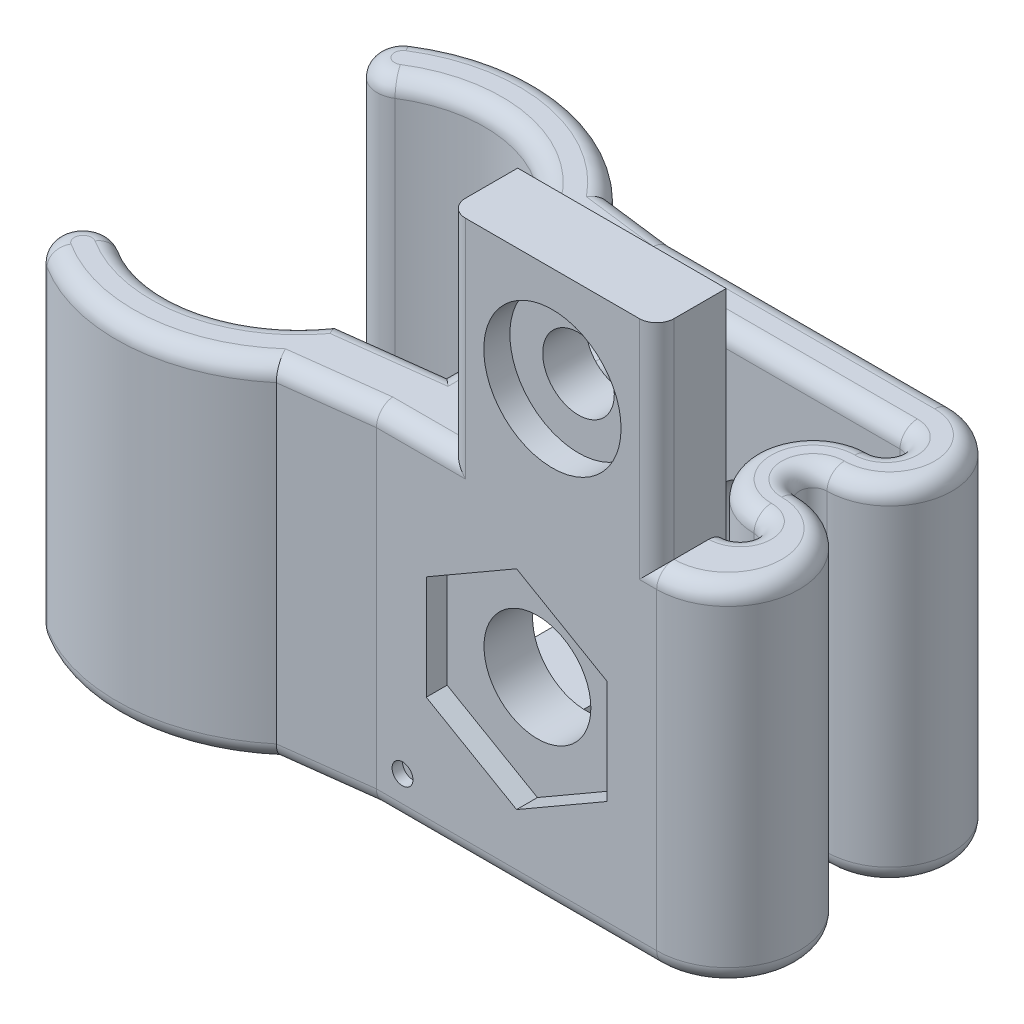
SolidWorks part; units mm, degrees
ref_plane "Front Plane" through (0, 0, 0) normal (0, 0, 1) x (1, 0, 0)
ref_plane "Top Plane" through (0, 0, 0) normal (0, 1, 0) x (1, 0, 0)
ref_plane "Right Plane" through (0, 0, 0) normal (1, 0, 0) x (0, 0, -1)
sketch "Sketch2" plane through (0, 0, 0) normal (0, 1, 0) x (1, 0, 0)
  line L0 (0, 0) -> (28, 0) construction
  line L1 (0, 0) -> (0, 1.6) construction
  line L2 (0, 0) -> (0, -1.6) construction
  line L3 (28, 0) -> (28, 5) construction
  line L4 (28, 0) -> (28, -5) construction
  line L5 (28, 5) -> (6, 5) construction
  line L6 (28, -5) -> (6, -5) construction
  line L7 (11.8739, 5) -> (28, 5)
  line L8 (11.8739, -5) -> (28, -5)
  line L9 (28, 8) -> (11.8739, 8)
  line L10 (28, -9) -> (11.8739, -9)
  line L11 (11.8739, 5) -> (6.2801, 5.7)
  line L12 (11.8739, 8) -> (7.919, 8.4949)
  line L13 (11.8739, -5) -> (6.2801, -5.7)
  line L14 (11.8739, -9) -> (6.7523, -9.6409)
  arc A0 (6.2801, 5.7) -> (-4, 7.9443) centre (0, 1.6) ccw
  arc A1 (6.2801, -5.7) -> (-4, -7.9443) centre (0, -1.6) cw
  arc A2 (28, 5) -> (28, 3.4) centre (28, 4.2) cw
  arc A3 (28, 3.4) -> (28, -3.4) centre (28, 0) ccw
  arc A4 (28, -3.4) -> (28, -5) centre (28, -4.2) cw
  arc A5 (-4, 7.9443) -> (-5.6, 10.482) centre (-4.8, 9.2131) cw
  arc A6 (-4, -7.9443) -> (-5.6, -10.482) centre (-4.8, -9.2131) ccw
  arc A7 (-5.6, 10.482) -> (7.919, 8.4949) centre (0, 1.6) cw
  arc A8 (-5.6, -10.482) -> (6.7523, -9.6409) centre (0, -1.6) ccw
  arc A9 (28, -9) -> (28, -0.8) centre (28, -4.9) ccw
  arc A10 (28, -0.8) -> (28, 0.8) centre (28, 0) cw
  arc A11 (28, 0.8) -> (28, 8) centre (28, 4.4) ccw
  dimension "D6" = 7.5
  dimension "D7" = 7.5
  dimension "D8" = 0.8
  dimension "D9" = 0.8
  dimension "D11" = 1.5
  dimension "D12" = 1.5
  dimension "D14" = 10.5
  dimension "D16" = 10.5
  dimension "D17" = 0.8
  dimension "D18" = 11.8739
  dimension "D1" = 1.6
  dimension "D2" = 1.6
  dimension "D3" = 28
  dimension "D4" = 5
  dimension "D5" = 5
  dimension "D10" = 4
  dimension "D13" = 3
  dimension "D15" = 4
  dimension "D19" = 0.7
extrude "Boss-Extrude1" add sketch "Sketch2" along normal blind 20
sketch "Sketch3" plane through (0, 0, -8) normal (0, 0, -1) x (-1, 0, 0)
  line L0 (-19.9369, 20) -> (-19.9369, 0) construction
  line L1 (-28, 20) -> (-11.8739, 20) construction
  line L2 (-28, 0) -> (-11.8739, 0) construction
  circle A0 centre (-19.9369, 10) radius 3.075
  dimension "D1" = 6.15
extrude "Cut-Extrude1" cut sketch "Sketch3" against normal through all
sketch "Sketch4" plane through (0, 0, 9) normal (0, 0, 1) x (1, 0, 0)
  line L0 (19.9369, 6.925) -> (19.9369, 13.075) construction
  line L2 (19.9369, 4) -> (25.1331, 7)
  line L3 (25.1331, 7) -> (25.1331, 13)
  line L4 (25.1331, 13) -> (19.9369, 16)
  line L5 (19.9369, 16) -> (14.7408, 13)
  line L6 (14.7408, 13) -> (14.7408, 7)
  line L7 (14.7408, 7) -> (19.9369, 4)
  circle A0 centre (19.9369, 10) radius 3.075 construction
  circle A1 centre (19.9369, 10) radius 6 construction
  dimension "D1" = 12
extrude "Cut-Extrude2" cut sketch "Sketch4" against normal blind 1.2
sketch "Sketch5" plane through (0, 20, 0) normal (0, 1, 0) x (1, 0, 0)
  line L0 (28, -5) -> (11.8739, -5) construction
  line L1 (28, -9) -> (16, -9)
  line L2 (28, -9) -> (28, -5)
  line L3 (28, -5) -> (16, -5)
  line L4 (16, -9) -> (16, -5)
  dimension "D1" = 12
extrude "Boss-Extrude2" add sketch "Sketch5" along normal blind 12
sketch "Sketch6" plane through (0, 0, 9) normal (0, 0, 1) x (1, 0, 0)
  line L0 (16, 26) -> (28, 26) construction
  line L1 (16, 32) -> (16, 20) construction
  line L2 (28, 32) -> (28, 20) construction
  circle A0 centre (22, 26) radius 2.06
  dimension "D1" = 4.12
extrude "Cut-Extrude3" cut sketch "Sketch6" against normal through all
sketch "Sketch7" plane through (0, 0, 0) normal (0, -1, 0) x (1, 0, 0)
  line L0 (11.8739, 5) -> (11.8739, -1.8)
  line L1 (28, 5) -> (11.8739, 5) construction
  line L2 (16.8739, 5) -> (16.8739, -2.3)
  line L3 (11.8739, 5) -> (16.8739, 5)
  line L4 (11.8739, -1.8) -> (16.8739, -2.3)
  dimension "D1" = 11.8739
  dimension "D2" = 6.8
  dimension "D3" = 7.3
  dimension "D4" = 5
extrude "Boss-Extrude3" add sketch "Sketch7" against normal blind 4
extrude "Boss-Extrude4" add sketch "Sketch7<2>" against normal blind 4 from offset 16 offset against normal yes
sketch "Sketch7<2>" plane through (0, 0, 0) normal (0, -1, 0) x (1, 0, 0) same geometry as "Sketch7"
sketch "Sketch8" plane through (0, 0, 9) normal (0, 0, 1) x (1, 0, 0)
  circle A0 centre (22, 26) radius 3.95
  dimension "D1" = 7.9
extrude "Cut-Extrude4" cut sketch "Sketch8" against normal blind 1.5
fillet "Fillet1" radius 1 23 edges at (24.6, 0, 0) (28.8, 0, 4.2) (22.4369, 0, 5) (16.8739, 0, 1.35) (14.3739, 0, -2.05) (11.8739, 0, 1.6) (1.5997, 0, 8.9274) (-6.0689, 0, 8.4131) (0.7133, 0, 12.0757) (19.9369, 0, 9) (32.1, 0, 4.9) (27.2, 0, 0) (31.6, 0, -4.4) (19.9369, 0, -8) (1.5269, 0, -11.9884) (-6.0689, 0, -8.4131) (1.5997, 0, -8.9274) (19.9369, 0, -5) (28.8, 0, -4.2) (9.8964, 0, -8.2475) (9.077, 0, -5.35) (9.077, 0, 5.35) (9.3131, 0, 9.3205)
fillet "Fillet7" radius 1 2 edges at (28, 26, 9)
fillet "Fillet10" radius 1 14 edges at (19.9369, 20, -8) (31.6, 20, -4.4) (27.2, 20, 0) (32.1, 20, 4.9) (27.5, 20, 9) (28.8, 20, 4.2) (24.6, 20, 0) (28.8, 20, -4.2) (19.9369, 20, -5) (9.077, 20, -5.35) (1.5997, 20, -8.9274) (-6.0689, 20, -8.4131) (1.5269, 20, -11.9884) (9.8964, 20, -8.2475)
fillet "Fillet11" radius 1 9 edges at (9.3131, 20, 9.3205) (0.7133, 20, 12.0757) (-6.0689, 20, 8.4131) (1.5997, 20, 8.9274) (9.077, 20, 5.35) (16.8739, 20, 1.35) (14.3739, 20, -2.05) (11.8739, 20, 1.6)
sketch "Sketch9" plane through (0, 0, 9) normal (0, 0, 1) x (1, 0, 0)
  line L0 (11.8739, 1) -> (28, 1) construction
  line L1 (11.8739, 19) -> (11.8739, 1) construction
  circle A0 centre (13.3739, 2.5) radius 0.6
  dimension "D1" = 1.2
  dimension "D2" = 1.5
  dimension "D3" = 1.5
extrude "Cut-Extrude5" cut sketch "Sketch9" against normal blind 0.6
